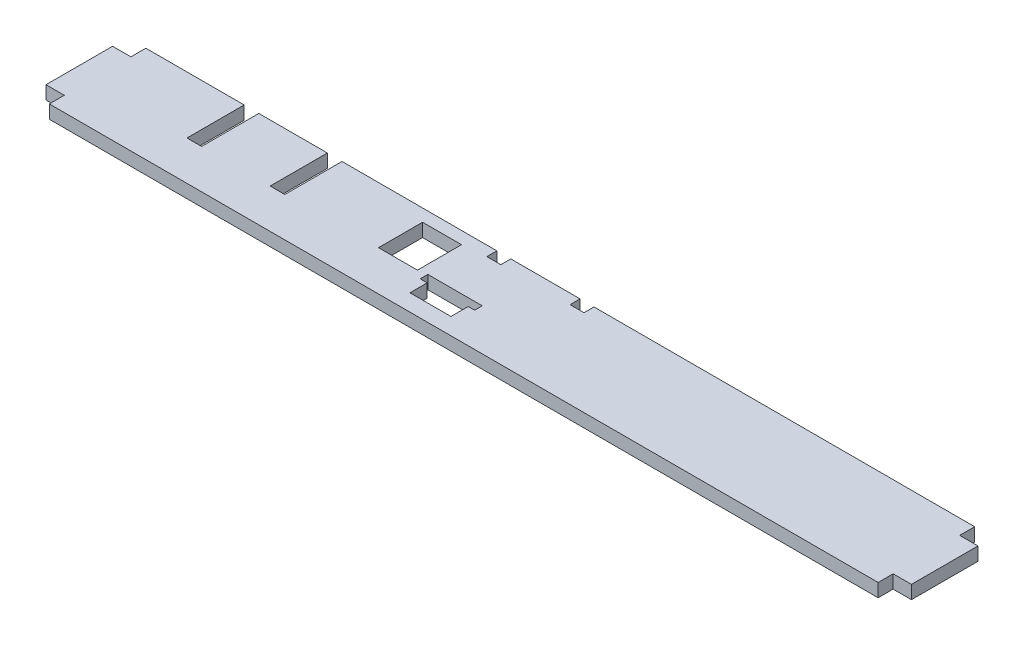
SolidWorks part; units mm, degrees
ref_plane "Спереди" through (0, 0, 0) normal (0, 0, 1) x (1, 0, 0)
ref_plane "Сверху" through (0, 0, 0) normal (0, 1, 0) x (1, 0, 0)
ref_plane "Справа" through (0, 0, 0) normal (1, 0, 0) x (0, 0, -1)
sketch "Эскиз1" plane through (0, 0, 0) normal (0, 1, 0) x (1, 0, 0)
  line L0 (-14.85, 14.4985) -> (5.95, 14.4985)
  line L1 (-124.5, -14.4985) -> (124.5, -14.4985)
  line L2 (-124.5, -14.4985) -> (-124.5, 14.4985)
  line L3 (-124.5, 14.4985) -> (-19.05, 14.4985)
  line L4 (124.5, -14.4985) -> (124.5, 14.4985)
  line L5 (-124.5, -14.4985) -> (124.5, 14.4985) construction
  line L6 (-124.5, 14.4985) -> (124.5, -14.4985) construction
  line L7 (-19.05, 14.4985) -> (-18.95, 14.4985) construction
  line L8 (-19.05, 14.4985) -> (-19.05, 11.4985)
  line L9 (-19.05, 11.4985) -> (-14.85, 11.4985)
  line L10 (-14.85, 14.4985) -> (-14.85, 11.4985)
  line L11 (5.95, 11.4985) -> (10.15, 11.4985)
  line L12 (5.95, 14.4985) -> (5.95, 11.4985)
  line L13 (10.15, 14.4985) -> (10.15, 11.4985)
  line L14 (10.15, 14.4985) -> (124.5, 14.4985)
  point P0 (0, 0)
  dimension "D1" = 28.997
  dimension "D2" = 249
  dimension "D3" = 4.2
  dimension "D4" = 3
  dimension "D5" = 0.1
  dimension "D6" = 2
extrude "Бобышка-Вытянуть1" add sketch "Эскиз1" along normal blind 4
sketch "Эскиз2" plane through (124.5, 0, 0) normal (1, 0, 0) x (0, 0, -1)
  line L0 (14.4985, 4) -> (-14.4985, 0) construction
  line L2 (-10, 4) -> (10, 4)
  line L3 (-10, 4) -> (-10, 0)
  line L4 (-10, 0) -> (10, 0)
  line L5 (10, 4) -> (10, 0)
  line L6 (-10, 4) -> (10, 0) construction
  line L7 (-10, 0) -> (10, 4) construction
  point P4 (0, 2)
  dimension "D1" = 4
  dimension "D2" = 20
extrude "Бобышка-Вытянуть2" add sketch "Эскиз2" along normal blind 5.5
mirror "Mirror1" about plane through (0, 0, 0) normal (1, 0, 0) of "Бобышка-Вытянуть2"
sketch "Sketch1" plane through (0, 4, 0) normal (0, 1, 0) x (1, 0, 0)
  line L0 (-19.05, 14.4985) -> (-124.5, 14.4985) construction
  line L1 (-69.9638, -2.6921) -> (-65.5638, -2.6921)
  line L2 (-69.9638, -2.6921) -> (-69.9638, 14.4985)
  line L3 (-69.9638, 14.4985) -> (-65.5638, 14.4985)
  line L4 (-65.5638, -2.6921) -> (-65.5638, 14.4985)
  line L5 (-69.9638, -2.5015) -> (-69.7638, -2.5015) construction
  dimension "D1" = 4.4
  dimension "D2" = 0.2
extrude "Cut-Extrude1" cut sketch "Sketch1" against normal blind 10
pattern_linear "LPattern1" count 2 spacing 25 along (-1, 0, 0) of "Cut-Extrude1"
sketch "Sketch2" plane through (0, 0, 0) normal (0, -1, 0) x (1, 0, 0)
  line L1 (-23.2847, 1.9997) -> (-6.9316, 1.9997)
  line L2 (-23.2847, 1.9997) -> (-23.2847, 4.289)
  line L3 (-23.2847, 4.289) -> (-6.9316, 4.289)
  line L4 (-6.9316, 1.9997) -> (-6.9316, 4.289)
  line L5 (-8.871, 9.4717) -> (-21.1883, 9.4717)
  line L6 (-8.871, 9.4717) -> (-8.871, 4.289)
  line L7 (-8.871, 4.289) -> (-21.1883, 4.289)
  line L8 (-21.1883, 9.4717) -> (-21.1883, 4.289)
sketch "Sketch3" plane through (0, 0, 0) normal (0, 1, 0) x (1, 0, 0)
  line L1 (-37.6507, -2.449) -> (-25.9648, -2.449)
  line L2 (-37.6507, -2.449) -> (-37.6507, 10.7875)
  line L3 (-37.6507, 10.7875) -> (-25.9648, 10.7875)
  line L4 (-25.9648, -2.449) -> (-25.9648, 10.7875)
extrude "Cut-Extrude3" cut sketch "Sketch3" along normal blind 10
extrude "Cut-Extrude4" cut sketch "Sketch2" against normal blind 10 contours L1 L4 L3 L2 | L5 L8 L3 L6 region at (-15.1082, 0, 3.1444) region at (-15.0296, 0, 6.8803)
